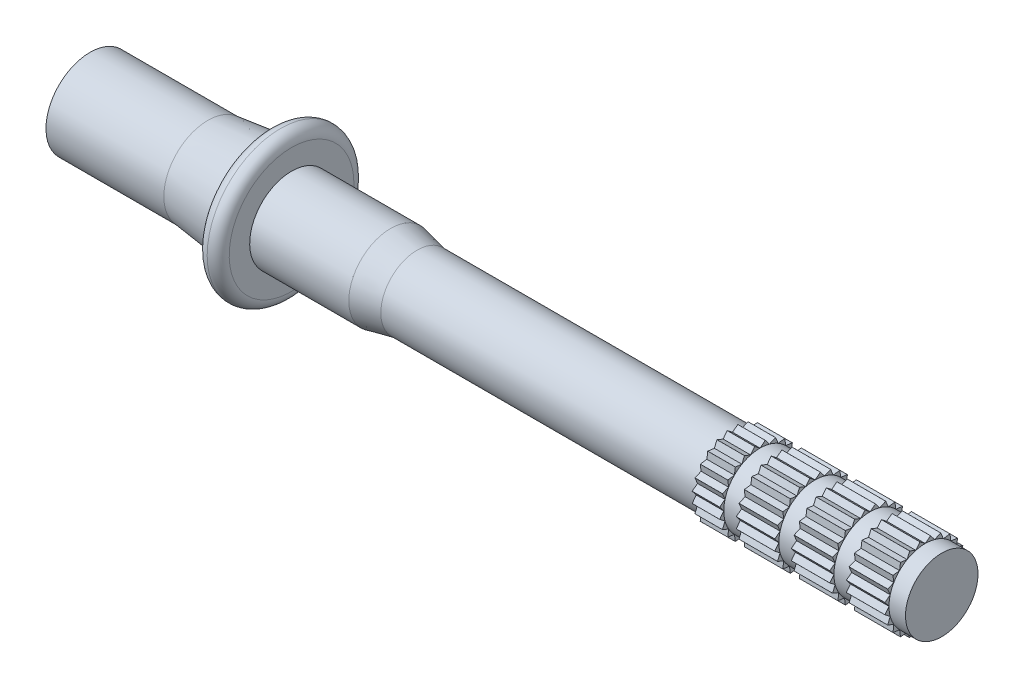
SolidWorks part; units mm, degrees
material "1.8515 (31CrMo12)"
ref_plane "Ön Düzlem" through (0, 0, 0) normal (0, 0, 1) x (1, 0, 0)
ref_plane "Üst Düzlem" through (0, 0, 0) normal (0, 1, 0) x (1, 0, 0)
ref_plane "Sağ Düzlem" through (0, 0, 0) normal (1, 0, 0) x (0, 0, -1)
sketch "Çizim1" plane through (0, 0, 0) normal (0, 0, 1) x (1, 0, 0)
  line L0 (0, 0) -> (0, 2)
  line L1 (0, 2) -> (5.35, 2)
  line L2 (5.35, 2) -> (8.15, 2.3314)
  line L3 (8.15, 2.3314) -> (8.15, 3.3314)
  line L4 (8.15, 3.3314) -> (9.15, 3.3314)
  line L5 (9.15, 3.3314) -> (9.15, 1.9014)
  line L6 (9.15, 1.9014) -> (13.65, 1.9014)
  line L7 (13.65, 1.9014) -> (14.85, 1.6463)
  line L8 (14.85, 1.6463) -> (29.17, 1.6463)
  line L9 (29.17, 1.6463) -> (29.17, 1.8463)
  line L10 (29.17, 1.8463) -> (38.67, 1.8463)
  line L11 (38.67, 1.8463) -> (38.67, 0)
  line L12 (38.67, 0) -> (0, 0)
  dimension "D1" = 2
  dimension "D2" = 5.35
  dimension "D3" = 2.8
  dimension "D4" = 173.25
  dimension "D5" = 1
  dimension "D6" = 1
  dimension "D7" = 1.43
  dimension "D8" = 168
  dimension "D9" = 1.2
  dimension "D10" = 0.2
  dimension "D11" = 4.5
  dimension "D12" = 14.32
  dimension "D13" = 9.5
revolve "Döndür1" add sketch "Çizim1" angle 360 about L12
sketch "Çizim2" plane through (38.67, 0, 0) normal (1, 0, 0) x (0, 0, -1)
  line L0 (0, 0) -> (0, 1.9014) construction
  line L1 (-0.2402, 1.8306) -> (0, 1.6463)
  line L2 (0, 1.6463) -> (0.2402, 1.8306)
  circle A0 centre (0, 0) radius 1.9014 construction
  circle A1 centre (0, 0) radius 1.8463 construction
  circle A2 centre (0, 0) radius 1.6463 construction
  arc A3 (-0.2402, 1.8306) -> (0.2402, 1.8306) centre (0, 1.4583) cw
  dimension "D1" = 105
extrude "Kes-Ekstrüzyon2" cut sketch "Çizim2" against normal blind 10
pattern_circular "Dairesel Kaplama1" count 24 over 360 about axis through (38.67, 0, 0) along (1, 0, 0) of "Kes-Ekstrüzyon2" reverse direction yes
sketch "Çizim3" plane through (38.67, 0, 0) normal (1, 0, 0) x (0, 0, -1)
  circle A0 centre (0, 0) radius 1.6463
extrude "Kes-Ekstrüzyon3" cut sketch "Çizim3" against normal blind 0.75 flip side to cut
pattern_linear "LÇoğaltma1" count 4 spacing 2.5 along (-1, 0, 0) of "Kes-Ekstrüzyon3"
fillet "Radyus1" radius 0.5 2 edges at (9.15, 3.3314, 0) (8.15, 3.3314, 0)
